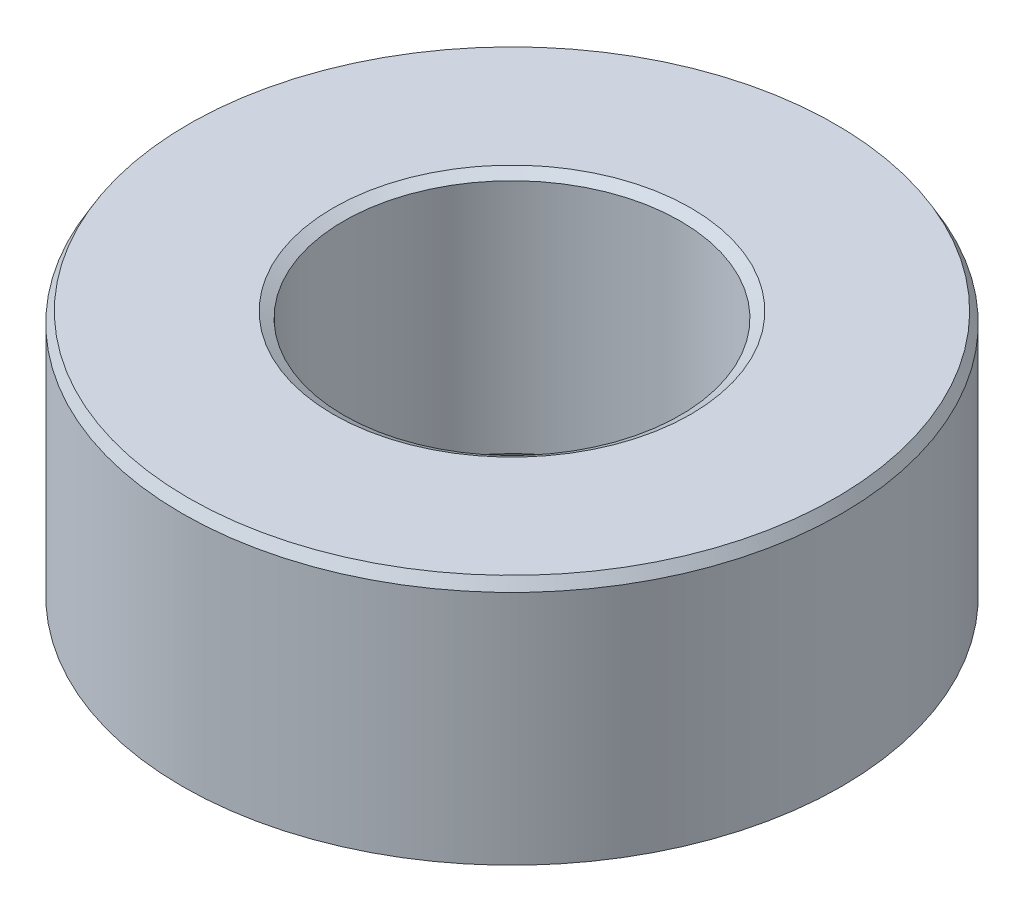
SolidWorks part; units mm, degrees
ref_plane "Front Plane" through (0, 0, 0) normal (0, 0, 1) x (1, 0, 0)
ref_plane "Top Plane" through (0, 0, 0) normal (0, 1, 0) x (1, 0, 0)
ref_plane "Right Plane" through (0, 0, 0) normal (1, 0, 0) x (0, 0, -1)
sketch "Sketch1" plane through (0, 0, 0) normal (0, 1, 0) x (1, 0, 0)
  circle A0 centre (0, 0) radius 10
  dimension "SLEEVE_OD" = 20
extrude "Boss-Extrude1" add sketch "Sketch1" along normal blind 7.6694
sketch "Sketch2" plane through (0, 0, 0) normal (0, 1, 0) x (1, 0, 0)
  circle A0 centre (0, 0) radius 5.1041
  dimension "BORE_D" = 10.2081
extrude "Cut-Extrude1" cut sketch "Sketch2" along normal through all
chamfer "Chamfer1" distance 0.3194 angle 30 4 edges at (0, 7.6694, 5.1041) (0, 0, 5.1041) (0, 0, 10) (0, 7.6694, 10) first distance on face at (0, 7.6694, 5.1041) first distance on face at (0, 0, 5.1041) first distance on face at (0, 7.6694, 10)
